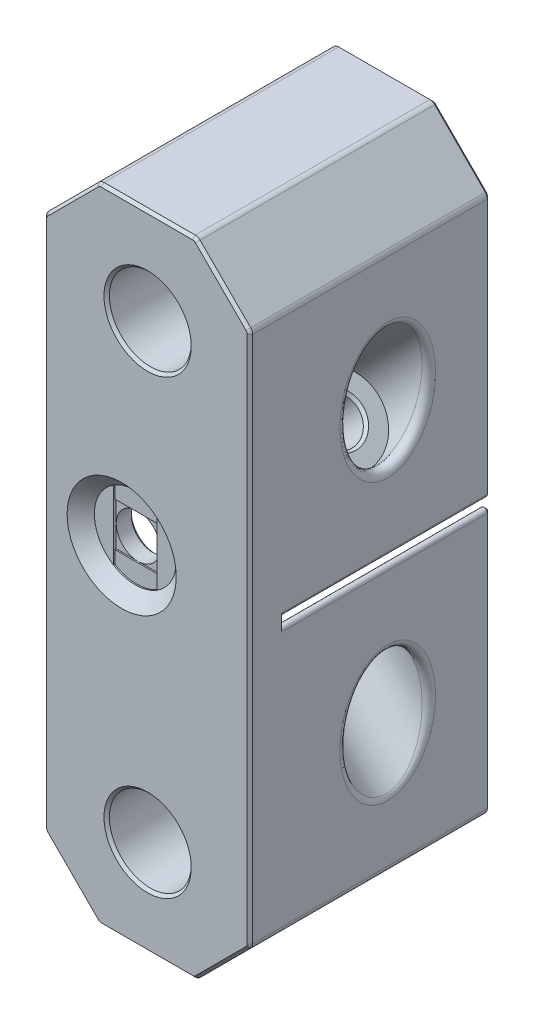
SolidWorks part; units mm, degrees
ref_plane "Front Plane" through (0, 0, 0) normal (1, 0, 0) x (0, 1, 0)
ref_plane "Top Plane" through (0, 0, 0) normal (0, 0, 1) x (0, 1, 0)
ref_plane "Right Plane" through (0, 0, 0) normal (0, 1, 0) x (-1, 0, 0)
sketch "Sketch1" plane through (0, 0, 0) normal (0, 0, 1) x (0, 1, 0)
  line L0 (0, 0) -> (-30.2, 30.2)
  line L1 (-30.2, 30.2) -> (-39.1, 30.2)
  line L2 (-47.1, 22.2) -> (-47.1, 8)
  line L3 (-39.1, 0) -> (39.1, 0)
  line L4 (47.1, 8) -> (47.1, 22.2)
  line L5 (39.1, 30.2) -> (12.7921, 30.2)
  line L6 (12.7921, 30.2) -> (21.496, 21.496)
  line L7 (21.496, 21.496) -> (0, 0)
  line L8 (-30.2, 30.2) -> (12.7921, 30.2)
  line L9 (2.6908, 18.8053) -> (10.748, 10.748) construction
  line L10 (6.9334, 14.5627) -> (10.748, 10.748) construction
  line L11 (2.6908, 24.8053) -> (2.6908, 30.2) construction
  line L12 (-39.1, 30.2) -> (-47.1, 22.2)
  line L13 (-47.1, 8) -> (-39.1, 0)
  line L14 (47.1, 22.2) -> (39.1, 30.2)
  line L15 (39.1, 0) -> (47.1, 8)
  circle A0 centre (-33.1, 15) radius 3.2
  circle A1 centre (-33.1, 15) radius 6
  circle A2 centre (33.1, 15) radius 3.2
  circle A3 centre (33.1, 15) radius 6
  circle A4 centre (2.6908, 18.8053) radius 3.2
  circle A5 centre (2.6908, 18.8053) radius 6
  point P3 (-47.1, 30.2)
  point P4 (-47.1, 0)
  point P5 (47.1, 0)
  point P6 (47.1, 30.2)
  point P15 (15.1, 15.1)
  point P17 (-15.1, 15.1)
  point P21 (6.9334, 14.5627)
  dimension "D5" = 6.4
  dimension "D6" = 12
  dimension "D1" = 30.4
  dimension "D2" = 30.2
  dimension "D3" = 30.2
  dimension "D4" = 45
  dimension "D7" = 14
  dimension "D8" = 14
  dimension "D9" = 18
  dimension "D10" = 18
  dimension "D11" = 15
extrude "Boss-Extrude1" add sketch "Sketch1" along normal blind 3 contours L8 L0 L7 L6 A5 | A5 A4 | L2 L3 L0 L1 A1 | L6 L7 L3 L4 L5 A3 region at (-0.5595, -19.55, 0) region at (-10.3524, 11.1437, 0) region at (-15.5234, -14.6766, 0) region at (-18.8053, -3.1395, 0)
extrude "Boss-Extrude4" add sketch "Sketch1<3>" against normal blind 30.2 contours L6 L7 L3 L4 L5 A3 region at (-10.3524, 11.1437, 0)
sketch "Sketch1<3>" plane through (0, 0, 0) normal (0, 0, 1) x (0, 1, 0) same geometry as "Sketch1"
extrude "Boss-Extrude5" add sketch "Sketch1<4>" along normal blind 2 from surface contours L8 L0 L7 L6 A5 | L2 L3 L0 L1 A1 | L6 L7 L3 L4 L5 A3 region at (-0.5595, -19.55, 0) region at (-10.3524, 11.1437, 0) region at (-15.5234, -14.6766, 0) starting at face at (-15.1, 0, 3)
sketch "Sketch1<4>" plane through (0, 0, 0) normal (0, 0, 1) x (0, 1, 0) same geometry as "Sketch1"
fillet "Fillet1" radius 0.5 2 edges at (0, 0, -15.1) (-30.2, 12.7921, -15.1)
extrude "Boss-Extrude6" add sketch "Sketch1<5>" against normal up to vertex (30.2 mm away) contours L2 L3 L0 L1 A1 region at (-0.5595, -19.55, 0) up to point (-21.4961, 21.4961, -30.2)
sketch "Sketch1<5>" plane through (0, 0, 0) normal (0, 0, 1) x (0, 1, 0) same geometry as "Sketch1"
fillet "Fillet2" radius 0.5 2 edges at (0, 0, -15.1) (-30.2, -30.2, -15.1)
extrude "Boss-Extrude7" add sketch "Sketch1<6>" along normal blind 3 from surface contours A3 A2 | A1 A0 region at (-15, -38.9303, 0) region at (-15, 27.2697, 0) starting at face at (-9, 33.1, -30.2)
sketch "Sketch1<6>" plane through (0, 0, 0) normal (0, 0, 1) x (0, 1, 0) same geometry as "Sketch1"
fillet "Fillet3" radius 1 8 edges at (0, 39.1, -12.6) (-8, 47.1, -12.6) (-22.2, 47.1, -12.6) (-30.2, 39.1, -12.6) (-30.2, -39.1, -12.6) (-22.2, -47.1, -12.6) (-8, -47.1, -12.6) (0, -39.1, -12.6)
chamfer "Chamfer1" distance 2 angle 45 1 edges at (-12.8053, 2.6908, 5)
sketch "Sketch2" plane through (0, 0, 3) normal (0, 0, 1) x (1, 0, 0)
  line L0 (-22.0053, 7.7662) -> (-22.0053, -2.3847)
  line L3 (-15.6053, 7.7662) -> (-15.6053, -2.3847)
  line L5 (-22.0053, 5.8908) -> (-15.6053, 5.8908)
  line L6 (-22.0053, 5.8908) -> (-22.0053, -0.5092)
  line L7 (-22.0053, -0.5092) -> (-15.6053, -0.5092)
  line L8 (-15.6053, 5.8908) -> (-15.6053, -0.5092)
  line L9 (-22.0053, 5.8908) -> (-15.6053, -0.5092) construction
  line L10 (-22.0053, -0.5092) -> (-15.6053, 5.8908) construction
  line L11 (-11.8, 28.0246) -> (-18.2, 28.0246)
  line L12 (-11.8, 28.0246) -> (-11.8, 38.1754)
  line L13 (-11.8, 38.1754) -> (-18.2, 38.1754)
  line L14 (-18.2, 28.0246) -> (-18.2, 38.1754)
  line L15 (-11.8, 28.0246) -> (-18.2, 38.1754) construction
  line L16 (-11.8, 38.1754) -> (-18.2, 28.0246) construction
  line L17 (-11.8, 29.9) -> (-18.2, 29.9)
  line L18 (-11.8, 29.9) -> (-11.8, 36.3)
  line L19 (-11.8, 36.3) -> (-18.2, 36.3)
  line L20 (-18.2, 29.9) -> (-18.2, 36.3)
  line L21 (-11.8, 29.9) -> (-18.2, 36.3) construction
  line L22 (-11.8, 36.3) -> (-18.2, 29.9) construction
  line L23 (-11.8, -38.1754) -> (-18.2, -38.1754)
  line L24 (-11.8, -38.1754) -> (-11.8, -28.0246)
  line L25 (-11.8, -28.0246) -> (-18.2, -28.0246)
  line L26 (-18.2, -38.1754) -> (-18.2, -28.0246)
  line L27 (-11.8, -38.1754) -> (-18.2, -28.0246) construction
  line L28 (-11.8, -28.0246) -> (-18.2, -38.1754) construction
  line L29 (-11.8, -36.3) -> (-18.2, -36.3)
  line L30 (-11.8, -36.3) -> (-11.8, -29.9)
  line L31 (-11.8, -29.9) -> (-18.2, -29.9)
  line L32 (-18.2, -36.3) -> (-18.2, -29.9)
  line L33 (-11.8, -36.3) -> (-18.2, -29.9) construction
  line L34 (-11.8, -29.9) -> (-18.2, -36.3) construction
  circle A0 centre (-18.8053, 2.6908) radius 3.2 construction
  circle A1 centre (-18.8053, 2.6908) radius 6
  circle A2 centre (-18.8053, 2.6908) radius 6
  circle A3 centre (-15, 33.1) radius 6
  circle A4 centre (-15, 33.1) radius 6
  circle A5 centre (-15, -33.1) radius 6
  circle A6 centre (-15, -33.1) radius 6
  circle A7 centre (-18.8053, 2.6908) radius 6 construction
  circle A8 centre (-15, 33.1) radius 3.2 construction
  circle A9 centre (-15, -33.1) radius 3.2 construction
  circle A10 centre (-15, -33.1) radius 3.2
  circle A11 centre (-15, -33.1) radius 6 construction
  circle M20 centre (-18.8053, 2.6908) radius 3.2
  circle M21 centre (-18.8053, 2.6908) radius 6
  dimension "D1" = 0
  dimension "D2" = 0
  dimension "D3" = 0
extrude "Cut-Extrude3" cut sketch "Sketch2" against normal blind 0.2 contours L0 L5 L3 M21 | L7 L0 L3 M21 | L5 L0 M20 | M20 | L5 L3 M20 | L7 L3 M20 | L0 L7 M20 region at (-18.8053, 7.1565, 3) region at (-21.2905, 5.176, 3) region at (-18.8053, -1.775, 3) region at (-21.2905, 0.2055, 3) region at (-18.8053, 2.6908, 3) region at (-16.3201, 5.176, 3) region at (-16.3201, 0.2055, 3)
extrude "Cut-Extrude4" cut sketch "Sketch2<3>" against normal blind 0.4 contours M20 | L5 L0 M20 | L5 L3 M20 | L7 L3 M20 | L0 L7 M20 region at (-21.2905, 5.176, 3) region at (-21.2905, 0.2055, 3) region at (-18.8053, 2.6908, 3) region at (-16.3201, 5.176, 3) region at (-16.3201, 0.2055, 3)
sketch "Sketch2<3>" plane through (0, 0, 3) normal (0, 0, 1) x (1, 0, 0) same geometry as "Sketch2"
extrude "Cut-Extrude5" cut sketch "Sketch2<4>" against normal blind 0.2 from surface contours L12 L19 L14 L17 | L19 L12 L13 L14 | L13 A4 | L12 L17 L14 L11 | L11 A4 | L31 L24 L25 L26 | L25 A6 | A10 L31 L32 | A10 | A10 L30 L31 | A10 L29 L24 | A10 L26 L29 | L24 L29 L26 L23 | L23 A6 region at (-15, 27.6522, 3) region at (-15, 28.9623, 3) region at (-15, 33.1, 3) region at (-15, 38.5478, 3) region at (-15, 37.2377, 3) region at (-15, -38.5478, 3) region at (-15, -37.2377, 3) region at (-12.5148, -35.5852, 3) region at (-17.4852, -35.5852, 3) region at (-15, -27.6522, 3) region at (-15, -28.9623, 3) region at (-12.5148, -30.6148, 3) region at (-15, -33.1, 3) region at (-17.4852, -30.6148, 3) starting at face at (-9, 33.1, -27.2)
sketch "Sketch2<4>" plane through (0, 0, 3) normal (0, 0, 1) x (1, 0, 0) same geometry as "Sketch2"
extrude "Cut-Extrude6" cut sketch "Sketch2<5>" against normal blind 0.2 from surface contours L12 L19 L14 L17 | A10 L31 L32 | A10 | A10 L30 L31 | A10 L29 L24 | A10 L26 L29 region at (-15, 33.1, 3) region at (-12.5148, -35.5852, 3) region at (-17.4852, -35.5852, 3) region at (-12.5148, -30.6148, 3) region at (-15, -33.1, 3) region at (-17.4852, -30.6148, 3) starting at face at (-15, 36.6689, -27.4)
sketch "Sketch2<5>" plane through (0, 0, 3) normal (0, 0, 1) x (1, 0, 0) same geometry as "Sketch2"
sketch "Sketch3" plane through (0, 0, 0) normal (-0.7071, -0.7071, 0) x (0.7071, -0.7071, 0)
  line L0 (-30.4, -30.2) -> (-1.2071, -30.2) construction
  line L1 (-30.4, -30.2) -> (-30.4, 0) construction
  circle A0 centre (-15.2, -15.2) radius 6
  circle A1 centre (-15.2, -15.2) radius 3.2
  dimension "D1" = 12
  dimension "D2" = 6.4
  dimension "D3" = 15
  dimension "D4" = 15.2
extrude "Cut-Extrude7" cut sketch "Sketch3" against normal through all contours A1 region at (-10.748, 10.748, -15.2)
extrude "Cut-Extrude8" cut sketch "Sketch3<3>" against normal through all from offset 5 contours A0 A1 region at (-14.8707, 14.8707, -15.2) offset against normal yes
sketch "Sketch3<3>" plane through (0, 0, 0) normal (-0.7071, -0.7071, 0) x (0.7071, -0.7071, 0) same geometry as "Sketch3"
sketch "Sketch4" plane through (0, 0, 0) normal (-0.7071, 0.7071, 0) x (-0.7071, -0.7071, 0)
  line L0 (1.2071, -30.2) -> (42.5021, -30.2) construction
  line L1 (0, -18.4) -> (0, -12) construction
  line L2 (0, -18.4) -> (0, -12)
  circle A0 centre (15.2, -15.2) radius 3.2
  circle A1 centre (15.2, -15.2) radius 6
  point P8 (0, 0)
  dimension "D1" = 6.4
  dimension "D2" = 12
  dimension "D3" = 15
  dimension "D4" = 15.2
extrude "Cut-Extrude9" cut sketch "Sketch4" against normal through all contours A0 region at (-10.748, -10.748, -15.2)
extrude "Cut-Extrude10" cut sketch "Sketch4<3>" against normal through all from offset 3 contours A1 A0 region at (-6.6254, -6.6254, -15.2) offset against normal yes
sketch "Sketch4<3>" plane through (0, 0, 0) normal (-0.7071, 0.7071, 0) x (-0.7071, -0.7071, 0) same geometry as "Sketch4"
chamfer "Chamfer2" distance 0.4 angle 45 52 edges at (0, 0, 0) (-11.8, 33.1, -30.2) (-11.8, -33.1, -30.2) (-25.4212, 17.5708, -30.2) (-29.8913, 13.5373, -30.2) (-30.2, 26.3425, -30.2) (-30.1239, 39.0685, -30.2) (-26.2, 43.1, -30.2) (-22.1685, 47.0239, -30.2) (-15.1, 47.1, -30.2) (-8.0315, 47.0239, -30.2) (-4, 43.1, -30.2) (-0.0761, 39.0685, -30.2) (0, 19.9464, -30.2) (-0.3087, 0.7452, -30.2) (-11.1748, 11.1748, -30.2) (-15.1, -47.1, -30.2) (-8.0315, -47.0239, -30.2) (-22.1685, -47.0239, -30.2) (-4, -43.1, -30.2) (-26.2, -43.1, -30.2) (-0.0761, -39.0685, -30.2) (-30.1239, -39.0685, -30.2) (0, -19.9464, -30.2) (-30.2, -34.5464, -30.2) (-0.3087, -0.7452, -30.2) (-30.1619, -30.2158, -30.2) (-15.4536, -15.4536, -30.2) (-15.6053, 2.6908, 0) (-30.2, -8.204, 0) (-9, -33.1, 5) (-4, -43.1, 5) (-8.0315, -47.0239, 5) (-0.0761, -39.0685, 5) (-15.1, -47.1, 5) (0, 0, 5) (-22.1685, -47.0239, 5) (-0.0761, 39.0685, 5) (-26.2, -43.1, 5) (-4, 43.1, 5) (-30.1239, -39.0685, 5) (-8.0315, 47.0239, 5) (-30.2, 0, 5) (-15.1, 47.1, 5) (-30.1239, 39.0685, 5) (-22.1685, 47.0239, 5) (-26.2, 43.1, 5) (-9, 33.1, 5) (-8.4853, 8.4853, -15.2) (-4.9497, 12.0208, -15.2) (-13.0108, -13.0108, -15.2) (-10.8894, -15.1321, -15.2)
fillet "Fillet4" radius 1 2 edges at (0, -13.0108, -15.2) (0, 13.0108, -15.2)
equation "\"D3@Sketch1\"=\"D2@Sketch1\""
equation "\"D8@Sketch1\"=\"D7@Sketch1\""
equation "\"D10@Sketch1\"=\"D9@Sketch1\""
